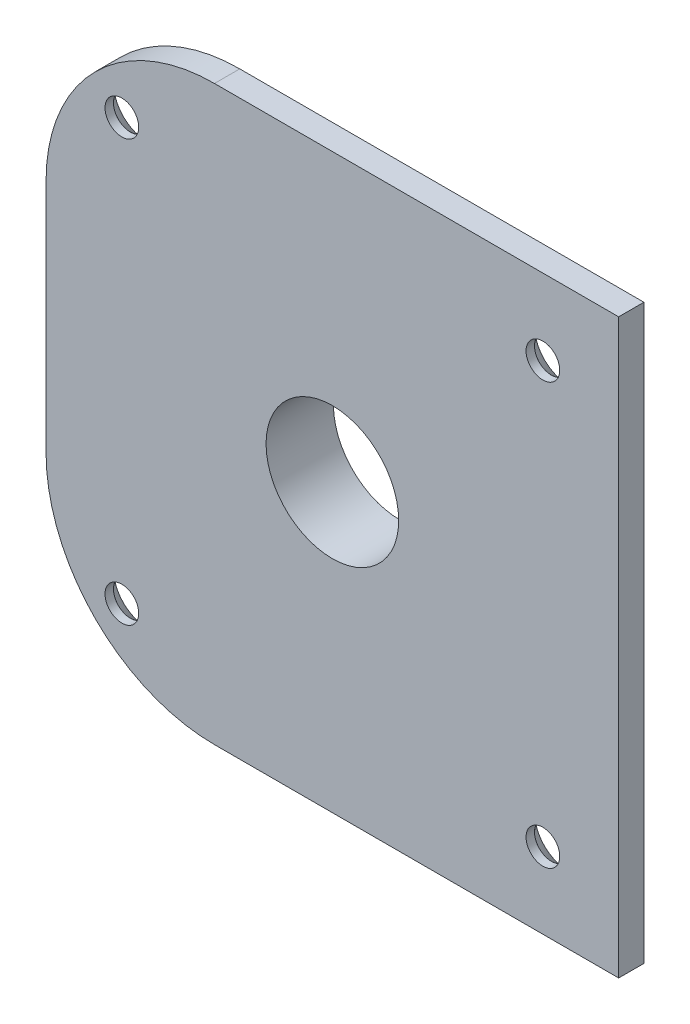
SolidWorks part; units mm, degrees
ref_plane "Front Plane" through (0, 0, 0) normal (0, 0, 1) x (1, 0, 0)
ref_plane "Top Plane" through (0, 0, 0) normal (0, 1, 0) x (1, 0, 0)
ref_plane "Right Plane" through (0, 0, 0) normal (1, 0, 0) x (0, 0, -1)
sketch "Sketch1" plane through (0, 0, 0) normal (0, 0, 1) x (1, 0, 0)
  line L1 (-34, -34) -> (34, -34)
  line L2 (-34, -34) -> (-34, 34)
  line L3 (-34, 34) -> (34, 34)
  line L4 (34, -34) -> (34, 34)
  line L5 (-34, -34) -> (34, 34) construction
  line L6 (-34, 34) -> (34, -34) construction
  line L7 (-25, -25) -> (25, -25) construction
  line L8 (-25, -25) -> (-25, 25) construction
  line L9 (-25, 25) -> (25, 25) construction
  line L10 (25, -25) -> (25, 25) construction
  line L11 (-25, -25) -> (25, 25) construction
  line L12 (-25, 25) -> (25, -25) construction
  circle A0 centre (25, 25) radius 2
  circle A1 centre (-25, 25) radius 2
  circle A2 centre (-25, -25) radius 2
  circle A3 centre (25, -25) radius 2
  circle A4 centre (0, 0) radius 7.875
  point P0 (0, 0)
  point P5 (0, 0)
  dimension "D3" = 4
  dimension "D4" = 15.75
  dimension "D1" = 68
  dimension "D2" = 9
extrude "Boss-Extrude1" add sketch "Sketch1" along normal blind 3
sketch "Sketch2" plane through (0, 0, 0) normal (0, 0, -1) x (-1, 0, 0)
  circle A0 centre (0, 0) radius 12.875
  circle A1 centre (0, 0) radius 7.875
  circle A2 centre (0, 0) radius 7.875 construction
  dimension "D1" = 5
extrude "Boss-Extrude2" add sketch "Sketch2" along normal blind 5
fillet "Fillet1" radius 20 2 edges at (-34, -34, 1.5) (-34, 34, 1.5)
fillet "Fillet2" radius 2 4 edges at (-23, 25, 0) (-23, -25, 0) (27, -25, 0) (27, 25, 0) conic rho 0.05
